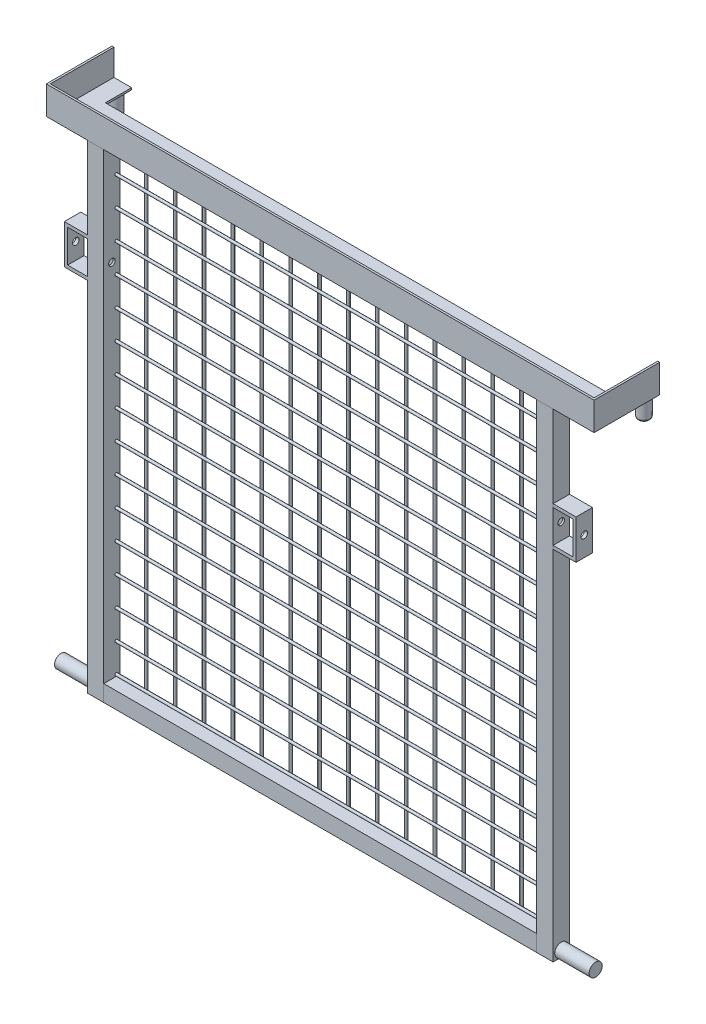
SolidWorks part; units mm, degrees
ref_plane "Piano frontale" through (0, 0, 0) normal (0, 0, 1) x (1, 0, 0)
ref_plane "Piano superiore" through (0, 0, 0) normal (0, 1, 0) x (1, 0, 0)
ref_plane "Piano destro" through (0, 0, 0) normal (1, 0, 0) x (0, 0, -1)
sketch "Schizzo1" plane through (0, 0, 0) normal (0, 1, 0) x (1, 0, 0)
  line L0 (-417.5, 100) -> (-417.5, 0)
  line L1 (-417.5, 0) -> (417.5, 0)
  line L2 (417.5, 0) -> (417.5, 100)
  line L3 (-417.5, 100) -> (-387.5, 100)
  line L4 (-387.5, 100) -> (-387.5, 60)
  line L5 (-387.5, 60) -> (387.5, 60)
  line L6 (387.5, 60) -> (387.5, 100)
  line L7 (387.5, 100) -> (417.5, 100)
  point P6 (0, 0)
  dimension "D1" = 30
  dimension "D2" = 30
  dimension "D3" = 100
  dimension "D4" = 100
  dimension "D5" = 835
  dimension "D6" = 60
extrude "Estrusione-Estrusione1" add sketch "Schizzo1" along normal blind 3
sketch "Schizzo2" plane through (0, 3, 0) normal (0, 1, 0) x (1, 0, 0)
  line L0 (417.5, 0) -> (417.5, 100) construction
  line L1 (-417.5, 0) -> (417.5, 0) construction
  line L2 (-417.5, 100) -> (-417.5, 0) construction
  line L3 (417.5, 0) -> (417.5, 100)
  line L4 (-417.5, 0) -> (417.5, 0)
  line L5 (-417.5, 100) -> (-417.5, 0)
  line L6 (-414.5, 100) -> (-414.5, 3)
  line L7 (-414.5, 3) -> (414.5, 3)
  line L8 (414.5, 3) -> (414.5, 100)
  line L9 (-417.5, 100) -> (-414.5, 100)
  line L10 (414.5, 100) -> (417.5, 100)
  dimension "D1" = 3
extrude "Estrusione-Estrusione2" add sketch "Schizzo2" along normal blind 40
sketch "Schizzo3" plane through (0, 0, 0) normal (0, 0, 1) x (1, 0, 0)
  line L0 (-355, 0) -> (-355, -730) construction
  line L1 (-417.5, 0) -> (417.5, 0) construction
  line L2 (-355, -730) -> (355, -730) construction
  line L3 (355, -730) -> (355, 0) construction
  point P4 (0, -730)
  dimension "D1" = 710
  dimension "D2" = 730
sketch "Schizzo4" plane through (0, 0, 0) normal (0, -1, 0) x (1, 0, 0)
  line L0 (-355, 0) -> (355, 0) construction
  line L1 (-355, 0) -> (-330, 0)
  line L2 (-355, 0) -> (-355, -25)
  line L3 (-355, -25) -> (-330, -25)
  line L4 (-330, 0) -> (-330, -25)
  line L5 (-352, -3) -> (-352, -22)
  line L6 (-352, -22) -> (-333, -22)
  line L7 (-333, -3) -> (-333, -22)
  line L8 (-352, -3) -> (-333, -3)
  line L9 (0, 0) -> (0, -60) construction
  line L10 (387.5, -60) -> (-387.5, -60) construction
  line L11 (352, -3) -> (333, -3)
  line L12 (333, -3) -> (333, -22)
  line L13 (352, -22) -> (333, -22)
  line L14 (352, -3) -> (352, -22)
  line L15 (330, 0) -> (330, -25)
  line L16 (355, -25) -> (330, -25)
  line L17 (355, 0) -> (355, -25)
  line L18 (355, 0) -> (330, 0)
  dimension "D1" = 25
  dimension "D2" = 25
  dimension "D3" = 3
extrude "Estrusione-Estrusione3" add sketch "Schizzo4" along normal blind 730 separate body
sketch "Schizzo5" plane through (-330, 0, 0) normal (1, 0, 0) x (0, 0, -1)
  line L0 (25, -730) -> (25, 0) construction
  line L1 (0, -730) -> (25, -730)
  line L2 (0, -730) -> (0, -705)
  line L3 (0, -705) -> (25, -705)
  line L4 (25, -730) -> (25, -705)
  line L5 (3, -708) -> (22, -708)
  line L6 (22, -727) -> (22, -708)
  line L7 (3, -727) -> (22, -727)
  line L8 (3, -727) -> (3, -708)
  dimension "D1" = 25
  dimension "D2" = 3
extrude "Estrusione-Estrusione4" add sketch "Schizzo5" along normal up to next separate body
sketch "Schizzo7" plane through (0, 0, 0) normal (0, -1, 0) x (1, 0, 0)
  line L1 (-330, -25) -> (-330, 0) construction
  line L2 (-288, -23) -> (-244, -23) construction
  line L3 (330, -25) -> (-330, -25) construction
  circle A0 centre (-288, -23) radius 2
  circle A1 centre (-244, -23) radius 2
  circle A2 centre (-200, -23) radius 2
  circle A3 centre (-156, -23) radius 2
  circle A4 centre (-112, -23) radius 2
  circle A5 centre (-68, -23) radius 2
  circle A6 centre (-24, -23) radius 2
  circle A7 centre (20, -23) radius 2
  circle A8 centre (64, -23) radius 2
  circle A9 centre (108, -23) radius 2
  circle A10 centre (152, -23) radius 2
  circle A11 centre (196, -23) radius 2
  circle A12 centre (240, -23) radius 2
  circle A13 centre (284, -23) radius 2
  dimension "D1" = 4
  dimension "D2" = 42
  dimension "D4" = 44
  dimension "D3" = 14
extrude "Estrusione-Estrusione5" add sketch "Schizzo7" along normal up to next separate body
sketch "Schizzo9" plane through (-330, 0, 0) normal (1, 0, 0) x (0, 0, -1)
  line L1 (0, 0) -> (100, 0) construction
  line L2 (19, -42) -> (19, -86) construction
  line L3 (21, 0) -> (21, -705) construction
  circle A0 centre (19, -42) radius 2
  circle A1 centre (19, -86) radius 2
  circle A2 centre (19, -130) radius 2
  circle A3 centre (19, -174) radius 2
  circle A4 centre (19, -218) radius 2
  circle A5 centre (19, -262) radius 2
  circle A6 centre (19, -306) radius 2
  circle A7 centre (19, -350) radius 2
  circle A8 centre (19, -394) radius 2
  circle A9 centre (19, -438) radius 2
  circle A10 centre (19, -482) radius 2
  circle A11 centre (19, -526) radius 2
  circle A12 centre (19, -570) radius 2
  circle A13 centre (19, -614) radius 2
  circle A14 centre (19, -658) radius 2
  circle A15 centre (19, -702) radius 2
  dimension "D1" = 4
  dimension "D2" = 42
  dimension "D4" = 44
  dimension "D3" = 16
extrude "Estrusione-Estrusione7" add sketch "Schizzo9" along normal up to next
sketch "Schizzo10" plane through (355, 0, 0) normal (1, 0, 0) x (0, 0, -1)
  line L0 (25, -730) -> (0, -730) construction
  circle A0 centre (12.5, -720) radius 10
  point P7 (12.5, -730)
  dimension "D1" = 20
extrude "Estrusione-Estrusione8" add sketch "Schizzo10" along normal blind 52.5 separate body
mirror "Specchia1" about plane through (0, 0, 0) normal (1, 0, 0) of bodies 138
sketch "Schizzo11" plane through (0, 0, 0) normal (0, 0, 1) x (1, 0, 0)
  line L0 (355, -125) -> (390, -125)
  line L1 (355, -730) -> (355, 0) construction
  line L2 (390, -125) -> (390, -185)
  line L3 (390, -185) -> (355, -185)
  line L4 (-417.5, 0) -> (417.5, 0) construction
  line L5 (355, -130) -> (385, -130)
  line L6 (385, -130) -> (385, -180)
  line L7 (385, -180) -> (355, -180)
  line L8 (355, -185) -> (355, -180)
  line L9 (355, -125) -> (355, -130)
  dimension "D1" = 60
  dimension "D2" = 35
  dimension "D3" = 125
  dimension "D4" = 5
extrude "Estrusione-Estrusione9" add sketch "Schizzo11" against normal up to surface (25 mm away) separate body up to face at (342.5, -365, -25)
sketch "Schizzo12" plane through (390, 0, 0) normal (1, 0, 0) x (0, 0, -1)
  line L0 (25, -125) -> (0, -125) construction
  line L1 (0, -185) -> (0, -125) construction
  circle A0 centre (12.5, -155) radius 5
  point P5 (12.5, -125)
  point P9 (0, -155)
  dimension "D1" = 10
extrude "Taglio-Estrusione1" cut sketch "Schizzo12" against normal up to surface (60 mm away) up to face at (330, -702, -21)
mirror "Specchia3" about plane through (0, 0, 0) normal (1, 0, 0) of "Taglio-Estrusione1", "Estrusione-Estrusione9"
sketch "Schizzo13" plane through (0, 0, 0) normal (0, -1, 0) x (1, 0, 0)
  line L0 (417.5, -100) -> (387.5, -100) construction
  circle A0 centre (402.5, -91) radius 9
  point P6 (402.5, -100)
  dimension "D1" = 18
extrude "Estrusione-Estrusione10" add sketch "Schizzo13" along normal blind 30 separate body
dome "Cupola1" faces to dome 1 distance 5 reverse direction no elliptical dome yes face at (402.5, -30, -100) parameters "D1"=5
mirror "Specchia5" about plane through (0, 0, 0) normal (1, 0, 0) of bodies 145
